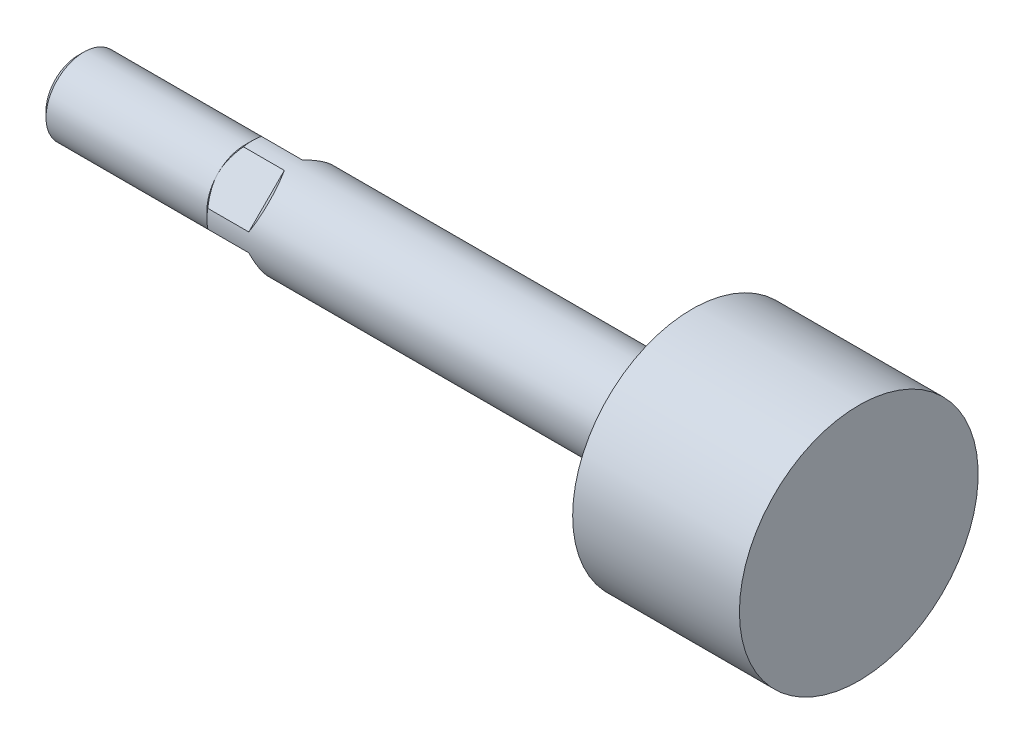
SolidWorks part; units mm, degrees
ref_plane "前视基准面" through (0, 0, 0) normal (0, 0, 1) x (1, 0, 0)
ref_plane "上视基准面" through (0, 0, 0) normal (0, 1, 0) x (1, 0, 0)
ref_plane "右视基准面" through (0, 0, 0) normal (1, 0, 0) x (0, 0, -1)
sketch "草图1" plane through (0, 0, 0) normal (0, 0, 1) x (1, 0, 0)
  line L0 (0, 0) -> (0, 4.233)
  line L1 (0, 4.233) -> (0.767, 5)
  line L2 (0.767, 5) -> (22, 5)
  line L3 (22, 5) -> (23, 6)
  line L4 (23, 6) -> (81, 6)
  line L5 (81, 6) -> (81, 15.75)
  line L6 (81, 15.75) -> (103, 15.75)
  line L7 (103, 15.75) -> (103, 0)
  line L8 (103, 0) -> (0, 0)
  line L9 (103, 0) -> (0, 0) construction
revolve "旋转1" add sketch "草图1" angle 360 about L9 reverse direction yes
cosmetic thread "装饰螺纹线1" parameters "D1"=22, "D2"=8.466
ref_plane "基准面4" through (30, 0, 0) normal (1, 0, 0) x (0, 0, -1)
ref_plane "基准面5" through (11, 0, 0) normal (1, 0, 0) x (0, 0, -1)
ref_plane "基准面6" through (0, 0, 0) normal (0, -0.7071, 0.7071) x (1, 0, 0)
sketch "草图2" plane through (0, 0, 0) normal (0, -0.7071, 0.7071) x (1, 0, 0)
  line L0 (-5, -12) -> (35.4, -12)
  line L1 (35.4, -12) -> (28.4, -5)
  line L2 (28.4, -5) -> (22, -5)
  line L3 (22, -5) -> (19.8, -7.2)
  line L4 (19.8, -7.2) -> (19.8, -10)
  line L5 (19.8, -10) -> (-3, -10)
  line L6 (-3, -10) -> (-3, 10)
  line L7 (-3, 10) -> (19.8, 10)
  line L8 (19.8, 10) -> (19.8, 7.2)
  line L9 (19.8, 7.2) -> (22, 5)
  line L10 (22, 5) -> (28.4, 5)
  line L11 (28.4, 5) -> (35.4, 12)
  line L12 (35.4, 12) -> (-5, 12)
  line L13 (-5, 12) -> (-5, -12)
extrude "切除-拉伸1" cut sketch "草图2" along normal blind 5 and the other way blind 5
ref_plane "基准面7" through (0, 0, 0) normal (0, -0.7071, -0.7071) x (-1, 0, 0)
sketch "草图3" plane through (0, 0, 0) normal (0, -0.7071, -0.7071) x (-1, 0, 0)
  line L0 (5, 12) -> (-35.4, 12)
  line L1 (-35.4, 12) -> (-28.4, 5)
  line L2 (-28.4, 5) -> (-22, 5)
  line L3 (-22, 5) -> (-19.8, 7.2)
  line L4 (-19.8, 7.2) -> (-19.8, 10)
  line L5 (-19.8, 10) -> (3, 10)
  line L6 (3, 10) -> (3, -10)
  line L7 (3, -10) -> (-19.8, -10)
  line L8 (-19.8, -10) -> (-19.8, -7.2)
  line L9 (-19.8, -7.2) -> (-22, -5)
  line L10 (-22, -5) -> (-28.4, -5)
  line L11 (-28.4, -5) -> (-35.4, -12)
  line L12 (-35.4, -12) -> (5, -12)
  line L13 (5, -12) -> (5, 12)
extrude "切除-拉伸2" cut sketch "草图3" along normal blind 5 and the other way blind 5
ref_plane "nut-rod XY" through (11, 0, 0) normal (-1, 0, 0) x (0, 0, 1)
ref_plane "nut-rod XZ" through (0, 0, 0) normal (0, 1, 0) x (1, 0, 0)
ref_plane "nut-rod YZ" through (0, 0, 0) normal (0, 0, -1) x (-1, 0, 0)
ref_axis "nut-rod X" through (11, 0, 80.9) along (0, 0, -1)
ref_axis "nut-rod Y" through (11, 50, 0) along (0, -1, 0)
ref_axis "nut-rod Z" through (-80.9, 0, 0) along (1, 0, 0)
sketch3d "nut-rod"
  point P0 (11, 0, 0)
ref_plane "rod XY" through (30, 0, 0) normal (-1, 0, 0) x (0, 0, 1)
ref_plane "rod XZ" through (0, 0, 0) normal (0, 1, 0) x (1, 0, 0)
ref_plane "rod YZ" through (0, 0, 0) normal (0, 0, -1) x (-1, 0, 0)
ref_axis "rod X" through (30, 0, 80.9) along (0, 0, -1)
ref_axis "rod Y" through (30, 50, 0) along (0, -1, 0)
ref_axis "rod Z" through (-80.9, 0, 0) along (1, 0, 0)
sketch3d "rod"
  point P0 (30, 0, 0)
